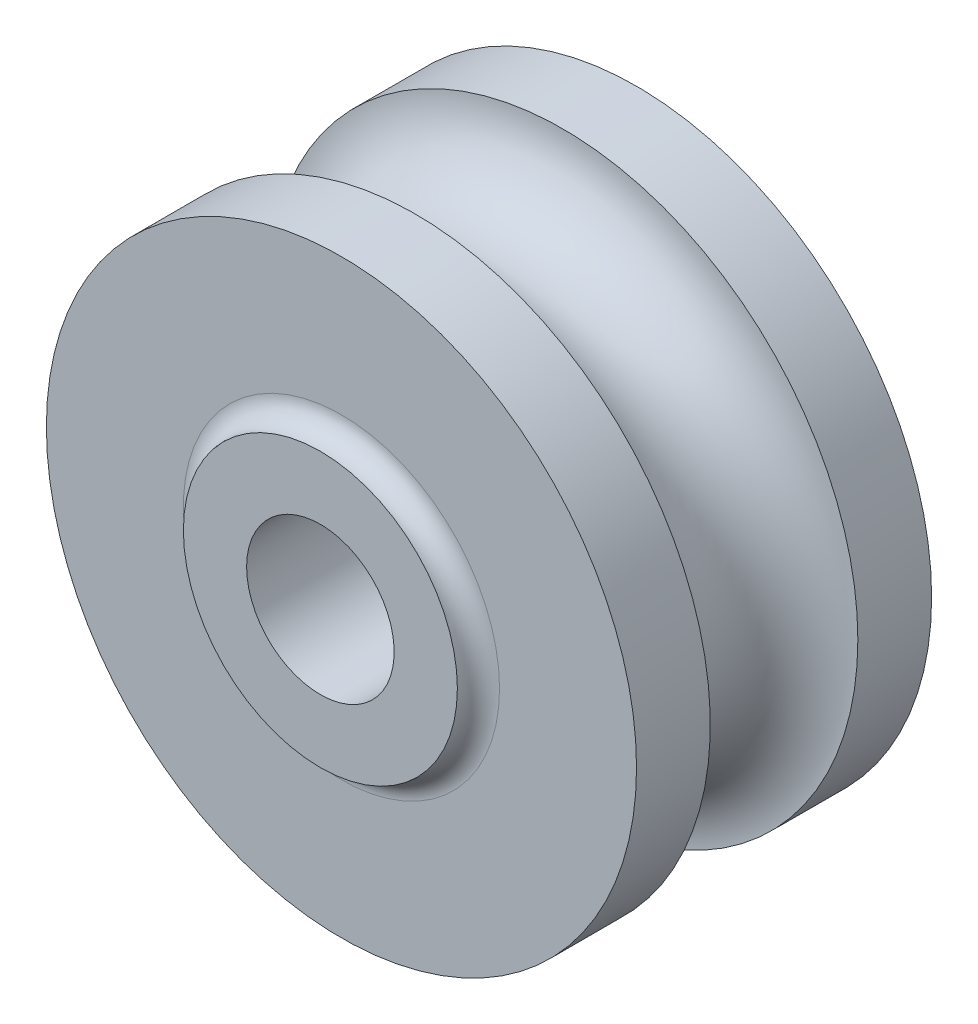
SolidWorks part; units mm, degrees
ref_plane "Front Plane" through (0, 0, 0) normal (0, 0, 1) x (1, 0, 0)
ref_plane "Top Plane" through (0, 0, 0) normal (0, 1, 0) x (1, 0, 0)
ref_plane "Right Plane" through (0, 0, 0) normal (1, 0, 0) x (0, 0, -1)
sketch "Sketch1" plane through (0, 0, 0) normal (0, 0, 1) x (1, 0, 0)
  circle A0 centre (0, 0) radius 28
  circle A1 centre (0, 0) radius 7
  dimension "D1" = 56
  dimension "D2" = 14
extrude "Boss-Extrude1" add sketch "Sketch1" along normal blind 28
sketch "Sketch2" plane through (0, 0, 0) normal (0, 0, -1) x (-1, 0, 0)
  circle A0 centre (0, 0) radius 13
  circle A1 centre (0, 0) radius 7 construction
  circle A2 centre (0, 0) radius 7
  dimension "D1" = 26
extrude "Boss-Extrude2" add sketch "Sketch2" along normal blind 2
ref_plane "Plane1" through (0, 0, 14) normal (0, 0, 1) x (1, 0, 0)
mirror "Mirror1" about plane through (0, 0, 14) normal (0, 0, 1) of "Boss-Extrude2"
sketch "Sketch3" plane through (0, 0, 0) normal (1, 0, 0) x (0, 0, -1)
  line L0 (0, 28) -> (-28, 28) construction
  line L1 (0, 0) -> (-43.735, 0) construction
  circle A0 centre (-14, 28) radius 7
  dimension "D1" = 14
revolve "Cut-Revolve1" cut sketch "Sketch3" angle 360 about L1
fillet "Fillet1" radius 2 1 edges at (13, 0, 0)
fillet "Fillet2" radius 2 1 edges at (13, 0, 28)
